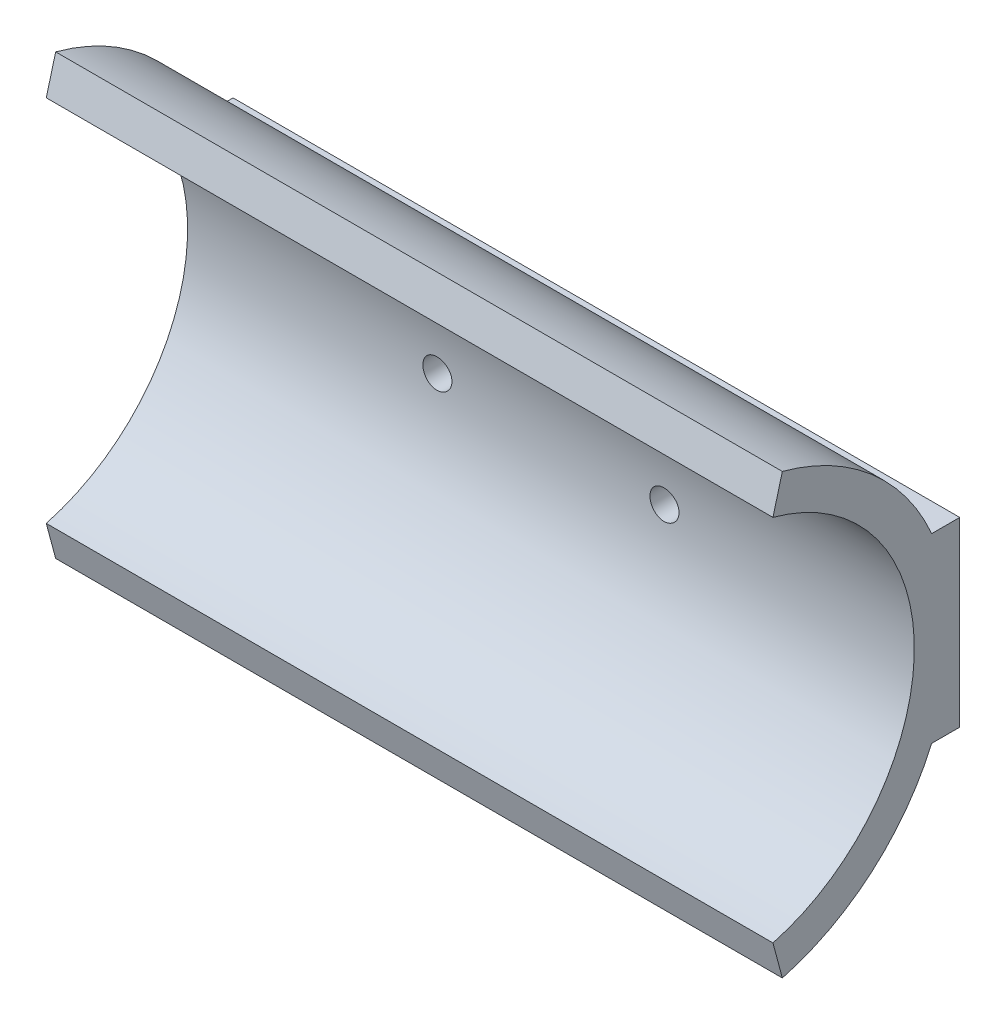
SolidWorks part; units mm, degrees
ref_plane "Front Plane" through (0, 0, 0) normal (1, 0, 0) x (0, 1, 0)
ref_plane "Top Plane" through (0, 0, 0) normal (0, 0, 1) x (0, 1, 0)
ref_plane "Right Plane" through (0, 0, 0) normal (0, 1, 0) x (-1, 0, 0)
sketch "Sketch1" plane through (0, 0, 0) normal (1, 0, 0) x (0, 1, 0)
  line L0 (20.2844, -5.4352) -> (24.1481, -6.4705)
  line L1 (-20.2844, -5.4352) -> (-24.1481, -6.4705)
  line L2 (0, 0) -> (57.6225, -15.4399) construction
  line L3 (0, 0) -> (38.6244, 0) construction
  line L4 (0, 0) -> (-49.8321, -13.3525) construction
  line L7 (-10, -22.9129) -> (-10, -26)
  line L8 (-10, -26) -> (10, -26)
  line L9 (10, -22.9129) -> (10, -26)
  line L10 (-10, -21) -> (10, -26) construction
  line L11 (-10, -26) -> (10, -21) construction
  arc A0 (-20.2844, -5.4352) -> (20.2844, -5.4352) centre (0, 0) ccw
  arc A1 (-24.1481, -6.4705) -> (-10, -22.9129) centre (0, 0) ccw
  arc A2 (10, -22.9129) -> (24.1481, -6.4705) centre (0, 0) ccw
  point P12 (0, -23.5)
  point P17 (0, -26.4058)
  point P18 (0, 0)
  point P19 (0, -23.5)
  point P20 (0, 0)
  point P23 (0, 0)
  point P24 (0, 0)
  point P25 (0, 0)
  point P26 (0, 0)
  point P27 (0, 0)
  dimension "D1" = 21
  dimension "D2" = 25
  dimension "D3" = 5
  dimension "D4" = 15
  dimension "D5" = 15
  dimension "D6" = 20
  dimension "D7" = 26
extrude "Boss-Extrude1" add sketch "Sketch1" along normal mid plane 80
sketch "Sketch2" plane through (0, 0, -26) normal (0, 0, -1) x (-1, 0, 0)
  line L0 (0, 0) -> (0, 14.4324) construction
  circle A0 centre (12.5, 0) radius 1.6
  circle A1 centre (-12.5, 0) radius 1.6
  point P6 (0, 0)
  point P8 (0, 0)
  point P9 (0, 0)
  dimension "D2" = 3.2
  dimension "D1" = 12.5
extrude "Cut-Extrude1" cut sketch "Sketch2" against normal through all both and the other way through all
